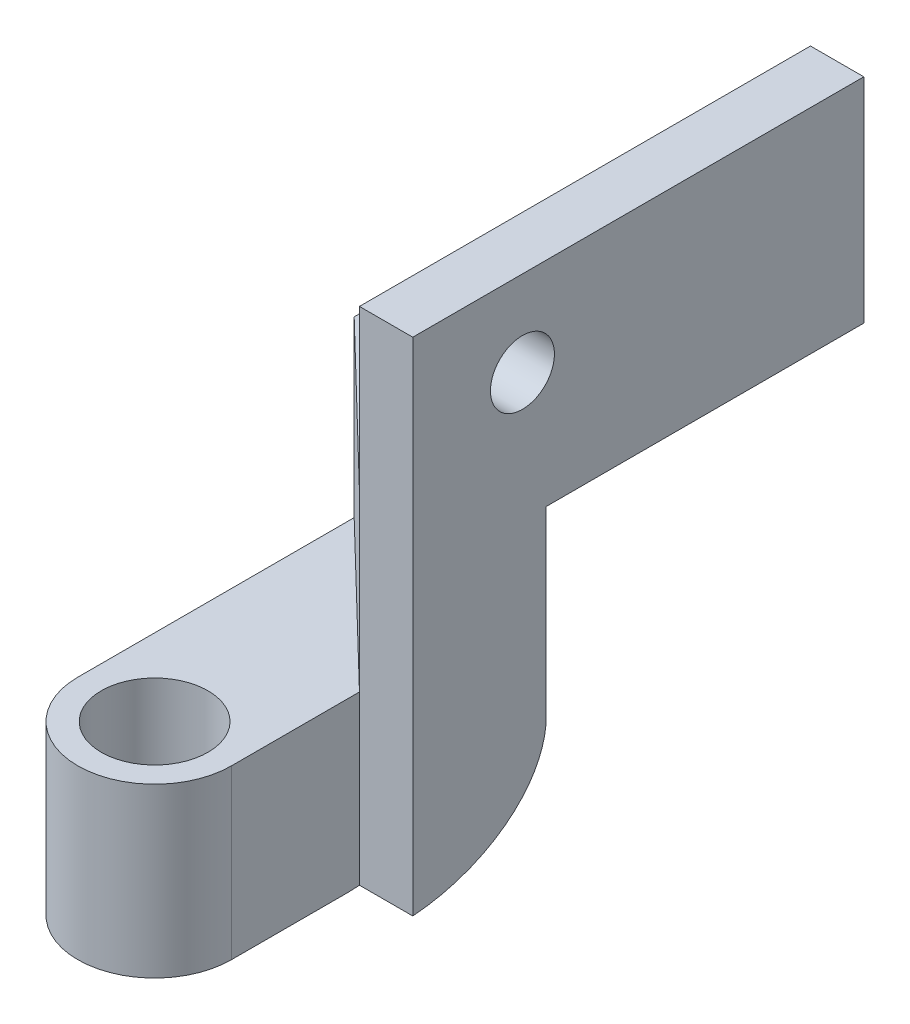
SolidWorks part; units mm, degrees
ref_plane "Front Plane" through (0, 0, 0) normal (0, 0, 1) x (1, 0, 0)
ref_plane "Top Plane" through (0, 0, 0) normal (0, 1, 0) x (1, 0, 0)
ref_plane "Right Plane" through (0, 0, 0) normal (1, 0, 0) x (0, 0, -1)
sketch "Croquis1" plane through (0, 0, 0) normal (0, 1, 0) x (1, 0, 0)
  line L3 (-3.6, 27.14) -> (-3.6, 0)
  line L4 (3.6, 0) -> (3.6, 27.14)
  line L5 (3.6, 27.14) -> (-3.6, 27.14)
  line L6 (-3.6, 12.953) -> (3.6, 6)
  line L7 (0, 0) -> (-2.5, 0) construction
  line L8 (-2.2862, 17.94) -> (3.6, 12.2557)
  line L9 (-2.2862, 17.94) -> (-3.6, 17.94)
  arc A3 (-3.6, 0) -> (3.6, 0) centre (0, 0) ccw
  circle A4 centre (0, 0) radius 2.5
  circle A5 centre (-0.4, 21.14) radius 1.5
  dimension "D1" = 3.6
  dimension "D6" = 5
  dimension "D10" = 3
  dimension "D2" = 27.14
  dimension "D3" = 9.2
  dimension "D7" = 44
  dimension "D8" = 6
  dimension "D9" = 4.5
  dimension "D11" = 6
  dimension "D12" = 4
extrude "Saliente-Extruir1" add sketch "Croquis1" against normal blind 2.5 contours L3 L8 L4 L5 A5 | L8 L3 L6 L4 region at (0, 0, -26.9747) region at (0.0596, 0, -12.4958)
extrude "Saliente-Extruir2" add sketch "Croquis1<4>" against normal blind 7.87 from offset 8.15 separate body contours L3 A3 L4 L6 A4 region at (-0.4356, 0, -4.4478) offset against normal yes
sketch "Croquis1<4>" plane through (0, 0, 0) normal (0, 1, 0) x (1, 0, 0) same geometry as "Croquis1"
extrude "Saliente-Extruir3" add sketch "Croquis1<5>" against normal up to surface (16.02 mm away) contours L8 L3 L6 L4 region at (0.0596, 0, -12.4958) up to face at (0, -16.02, 2.5)
sketch "Croquis1<5>" plane through (0, 0, 0) normal (0, 1, 0) x (1, 0, 0) same geometry as "Croquis1"
fillet "Redondeo1" radius 5 1 edges at (0.6569, -16.02, -15.0979)
sketch "Croquis3" plane through (3.6, 0, 0) normal (1, 0, 0) x (0, 0, -1)
  line L0 (6, -8.15) -> (6, -15.9949)
  line L1 (27.14, 7.5) -> (6, 7.5)
  line L8 (0, -16.02) -> (5.3049, -16.02)
  line L9 (12.2557, -11.02) -> (12.2557, -2.5)
  line L10 (12.2557, -2.5) -> (27.14, -2.5)
  line L11 (27.14, -2.5) -> (27.14, 0)
  line L12 (27.14, 0) -> (6, 0)
  line L13 (6, 0) -> (6, -8.15)
  line L14 (6, -8.15) -> (0, -8.15)
  line L15 (0, -8.15) -> (0, -16.02)
  line L16 (0, -16.02) -> (5.3049, -16.02)
  line L17 (12.2557, -11.02) -> (12.2557, -2.5)
  line L18 (12.2557, -2.5) -> (27.14, -2.5)
  line L19 (27.14, -2.5) -> (27.14, 7.5)
  line L21 (6, 7.5) -> (6, -8.15)
  line L22 (6, -8.15) -> (0, -8.15)
  line L23 (0, -8.15) -> (0, -16.02)
  circle A0 centre (11.14, 3.5) radius 1.5
  ellipse E1 centre (5.3049, -11.02) end of major axis (12.2557, -11.02) minor radius 5 (5.3049, -16.02) -> (12.2557, -11.02) ccw
  ellipse E2 centre (5.3049, -11.02) end of major axis (12.2557, -11.02) minor radius 5 (5.3049, -16.02) -> (12.2557, -11.02) ccw
  ellipse M2 centre (5.3049, -11.02) end of major axis (12.2557, -11.02) minor radius 5 (5.3049, -16.02) -> (12.2557, -11.02) ccw
  line M3 (12.2557, -11.02) -> (12.2557, -2.5)
  line M4 (12.2557, -2.5) -> (27.14, -2.5)
  line M5 (27.14, -2.5) -> (27.14, 0)
  line M6 (27.14, 0) -> (6, 0)
  line M7 (6, 0) -> (6, -8.15)
  dimension "D5" = 3
  dimension "D2" = 10
  dimension "D3" = 16
  dimension "D4" = 4
  dimension "D1" = 0
extrude "Saliente-Extruir4" add sketch "Croquis3" along normal blind 2.5 contours L0 M7 M2 M3 M4 M5 M6 | L1 L21 L19 A0 M6 region at (3.6, -5.6795, -12.0634) region at (3.6, 3.7617, -16.8234)
equation "\"D1@Saliente-Extruir2\"=7.87"
